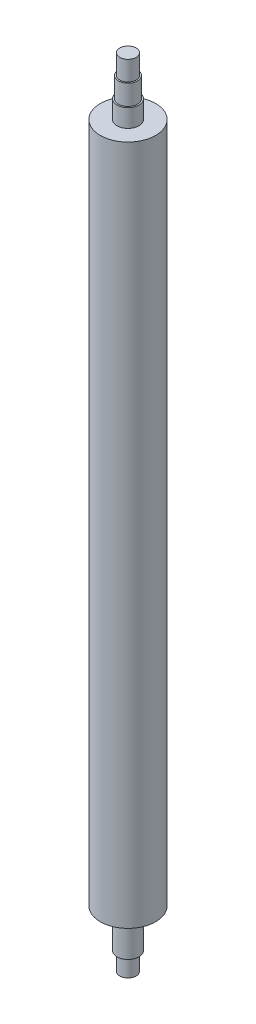
SolidWorks part; units mm, degrees
material "Stainless Steel (ferritic)"
ref_plane "Front Plane" through (0, 0, 0) normal (0, 0, 1) x (1, 0, 0)
ref_plane "Top Plane" through (0, 0, 0) normal (0, 1, 0) x (1, 0, 0)
ref_plane "Right Plane" through (0, 0, 0) normal (1, 0, 0) x (0, 0, -1)
sketch "Sketch1" plane through (0, 0, 0) normal (0, 1, 0) x (1, 0, 0)
  circle A0 centre (0, 0) radius 3.965
  circle A1 centre (0, 0) radius 3.45
  circle A2 centre (0, 0) radius 2.95
  circle A3 centre (0, 0) radius 10
  dimension "D1" = 7.93
  dimension "D2" = 6.9
  dimension "D3" = 5.9
  dimension "D4" = 20
extrude "Boss-Extrude8" add sketch "Sketch1" along normal blind 246 contours A3
extrude "Boss-Extrude9" add sketch "Sketch1<9>" against normal blind 14 contours A0
sketch "Sketch1<9>" plane through (0, 0, 0) normal (0, 1, 0) x (1, 0, 0) same geometry as "Sketch1"
extrude "Boss-Extrude10" add sketch "Sketch1<10>" against normal blind 6.5 from surface contours A2 region at (0, 0, 0) starting at face at (0, -14, 3.965)
sketch "Sketch1<10>" plane through (0, 0, 0) normal (0, 1, 0) x (1, 0, 0) same geometry as "Sketch1"
extrude "Boss-Extrude11" add sketch "Sketch1<11>" along normal blind 6.5 from surface contours A0 starting at face at (0, 246, 10)
sketch "Sketch1<11>" plane through (0, 0, 0) normal (0, 1, 0) x (1, 0, 0) same geometry as "Sketch1"
extrude "Boss-Extrude12" add sketch "Sketch1<12>" along normal blind 7.3 from surface contours A1 starting at face at (0, 252.5, 3.965)
sketch "Sketch1<12>" plane through (0, 0, 0) normal (0, 1, 0) x (1, 0, 0) same geometry as "Sketch1"
extrude "Boss-Extrude13" add sketch "Sketch1<13>" along normal blind 7.1 from surface contours A2 starting at face at (0, 259.8, 3.45)
sketch "Sketch1<13>" plane through (0, 0, 0) normal (0, 1, 0) x (1, 0, 0) same geometry as "Sketch1"
